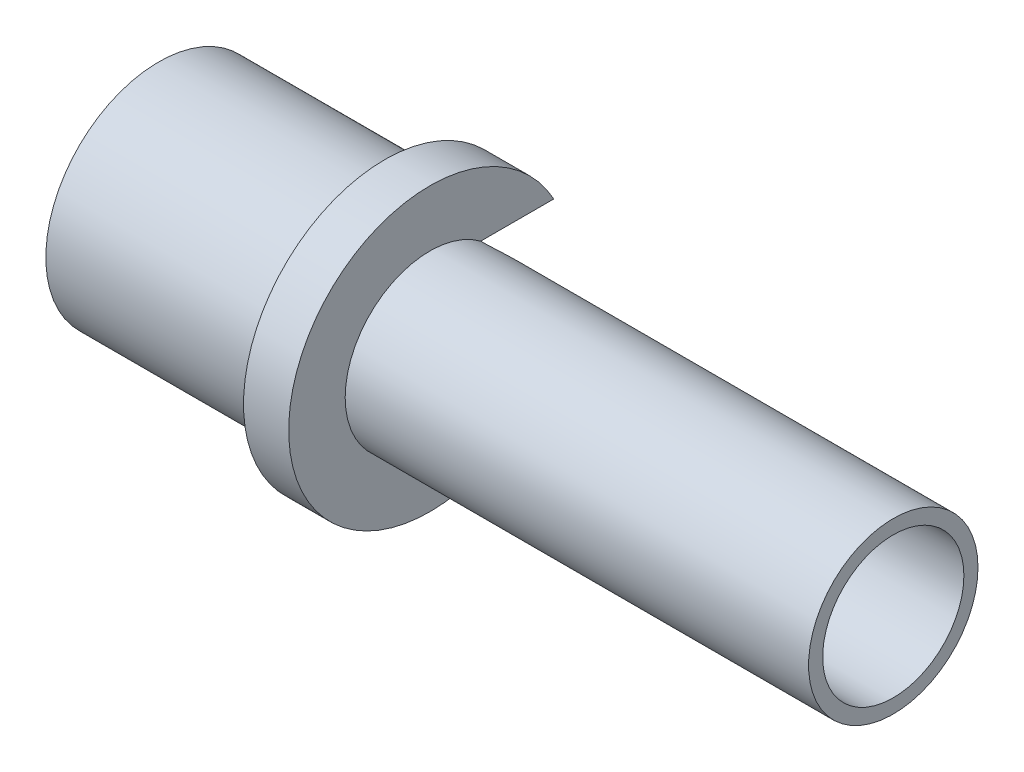
SolidWorks part; units mm, degrees
material "6061-T6 (SS)"
ref_plane "Front Plane" through (0, 0, 0) normal (0, 0, 1) x (1, 0, 0)
ref_plane "Top Plane" through (0, 0, 0) normal (0, 1, 0) x (1, 0, 0)
ref_plane "Right Plane" through (0, 0, 0) normal (1, 0, 0) x (0, 0, -1)
sketch "Sketch1" plane through (0, 0, 0) normal (0, 0, 1) x (1, 0, 0)
  line L0 (0, 0) -> (-16.6687, 0) construction
  line L1 (3.19, 3.9687) -> (3.19, 4.7625)
  line L2 (3.19, 4.7625) -> (-22.86, 4.7625)
  line L3 (-22.86, 4.7625) -> (-22.86, 7.9375)
  line L4 (-22.86, 7.9375) -> (-25.4, 7.9375)
  line L5 (-25.4, 7.9375) -> (-25.4, 6.35)
  line L6 (-25.4, 6.35) -> (-38.1, 6.35)
  line L7 (-38.1, 6.35) -> (-38.1, 3.9687)
  line L8 (-38.1, 3.9687) -> (3.19, 3.9687)
  line L9 (-25.4, -13.6525) -> (-25.4, 13.6525) construction
  line L14 (3.19, -11.375) -> (3.19, 11.375) construction
  point P9 (-2.7157, 4.7625)
  point P14 (24.9911, 3.9687)
  dimension "D1" = 7.9375
  dimension "D4" = 12.7
  dimension "D3" = 9.525
  dimension "D2" = 2.54
  dimension "D5" = 1.5875
  dimension "D6" = 12.7
revolve "Revolve1" add sketch "Sketch1" angle 360 about L0
sketch "Sketch2" plane through (3.19, 0, 0) normal (1, 0, 0) x (0, 0, -1)
  line L0 (1.3441, 3.7342) -> (7.0042, 3.7342)
  line L1 (7.0042, -3.7342) -> (1.3441, -3.7342)
  line L2 (0, 0) -> (14.3216, 0) construction
  circle A0 centre (0, 0) radius 3.9687 construction
  circle A1 centre (0, 0) radius 7.9375 construction
  arc A2 (1.3441, 3.7342) -> (1.3441, -3.7342) centre (0, 0) cw
  arc A3 (7.0042, 3.7342) -> (7.0042, -3.7342) centre (0, 0) cw
  arc A4 (3.6742, 3.7342) -> (3.6742, -3.7342) centre (0, 0) cw construction
  circle A5 centre (5.2387, 0) radius 1.27 construction
  circle A6 centre (4.623, 2.4642) radius 1.27 construction
  circle A7 centre (4.623, -2.4642) radius 1.27 construction
  dimension "D1" = 1.27
  dimension "D2" = 2.54
extrude "Cut-Extrude1" [suppressed] cut sketch "Sketch2" against normal through all both
sketch "Sketch3" plane through (0, 0, 0) normal (0, 0, 1) x (1, 0, 0)
  line L0 (-38.1, 3.81) -> (-38.1, -3.81)
  line L1 (-38.1, 6.35) -> (-38.1, -6.35) construction
  line L2 (-38.1, -3.81) -> (-22.86, -3.81)
  line L4 (-22.86, 3.81) -> (-38.1, 3.81)
  line L5 (-19.685, -0.635) -> (-19.685, 0.635)
  line L6 (-19.685, 0) -> (0, 0) construction
  line L8 (-22.86, -7.9375) -> (-22.86, 7.9375) construction
  arc A1 (-22.86, -3.81) -> (-19.685, -0.635) centre (-22.86, -0.635) ccw
  arc A2 (-19.685, 0.635) -> (-22.86, 3.81) centre (-22.86, 0.635) ccw
  point P6 (-25.4, -3.81)
  point P7 (-22.86, -3.81)
  dimension "D1" = 7.62
  dimension "D2" = 3.175
extrude "Cut-Extrude2" cut sketch "Sketch3" against normal up to next
equation "\"bearing1\"=0.273438"
equation "\"D1@Sketch1\"=5/16"
